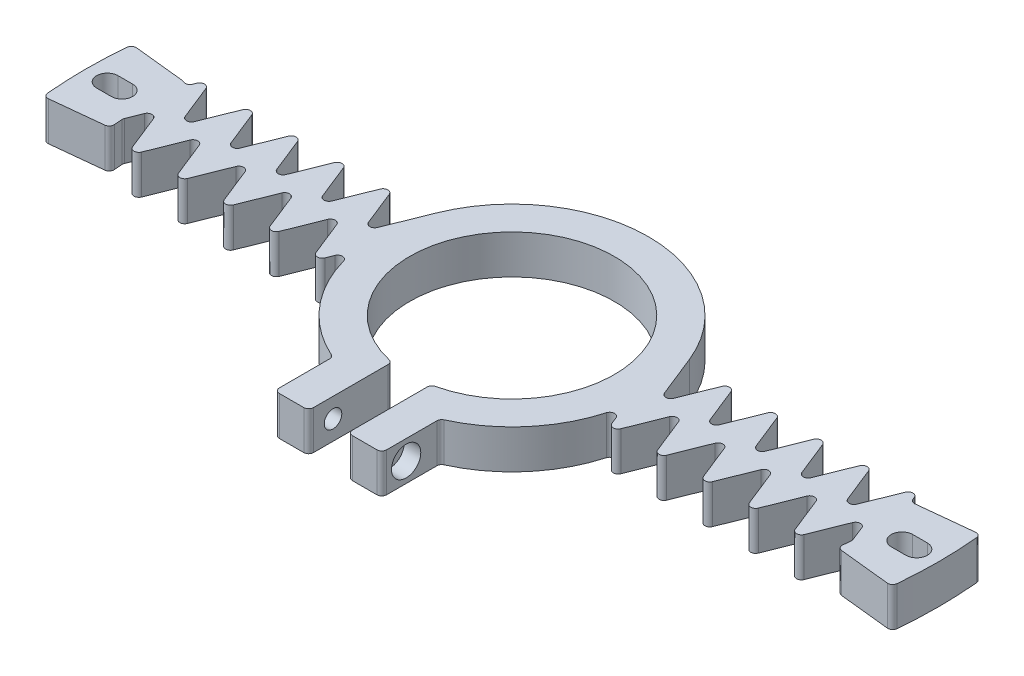
SolidWorks part; units mm, degrees
ref_plane "前视基准面" through (0, 0, 0) normal (0, 0, 1) x (1, 0, 0)
ref_plane "上视基准面" through (0, 0, 0) normal (0, 1, 0) x (1, 0, 0)
ref_plane "右视基准面" through (0, 0, 0) normal (1, 0, 0) x (0, 0, -1)
other "Configuration Table"
sketch "草图1" plane through (0, 0, 0) normal (0, 1, 0) x (1, 0, 0)
  line L0 (-1012, 0) -> (0, 0) construction
  line L1 (28, 0) -> (30.35, -5.8794) construction
  line L2 (30.35, -5.8794) -> (35.05, 5.8794) construction
  line L3 (35.05, 5.8794) -> (39.75, -5.8794) construction
  line L4 (39.75, -5.8794) -> (44.45, 5.8794) construction
  line L5 (44.45, 5.8794) -> (49.15, -5.8794) construction
  line L6 (49.15, -5.8794) -> (53.85, 5.8794) construction
  line L7 (53.85, 5.8794) -> (58.55, -5.8794) construction
  line L8 (58.55, -5.8794) -> (63.25, 5.8794) construction
  line L9 (63.25, 5.8794) -> (67.95, -5.8794) construction
  line L10 (67.95, -5.8794) -> (72.65, 5.8794) construction
  line L11 (72.65, 5.8794) -> (75, 0) construction
  line L12 (28, 0) -> (75, 0) construction
  line L15 (-4, -20.6155) -> (-4, -37.7128)
  line L16 (0, 0) -> (0, -50000) construction
  line L17 (11, -37.7128) -> (11, -25.7488)
  line L20 (87.0207, -9.1462) -> (74.5891, -7.8396)
  line L21 (87.0207, 9.1462) -> (74.5891, 7.8396)
  line L22 (-28, 0) -> (-75, 0) construction
  line L23 (-72.65, 5.8794) -> (-75, 0) construction
  line L24 (-67.95, -5.8794) -> (-72.65, 5.8794) construction
  line L29 (-63.25, 5.8794) -> (-67.95, -5.8794) construction
  line L30 (-58.55, -5.8794) -> (-63.25, 5.8794) construction
  line L31 (27.6386, -4.4844) -> (30.35, -11.268)
  line L32 (30.35, -11.268) -> (35.05, 0.4907)
  line L33 (35.05, 0.4907) -> (39.75, -11.268)
  line L34 (39.75, -11.268) -> (44.45, 0.4907)
  line L35 (44.45, 0.4907) -> (49.15, -11.268)
  line L36 (49.15, -11.268) -> (53.85, 0.4907)
  line L37 (53.85, 0.4907) -> (58.55, -11.268)
  line L38 (58.55, -11.268) -> (63.25, 0.4907)
  line L39 (63.25, 0.4907) -> (67.95, -11.268)
  line L40 (67.95, -11.268) -> (72.65, 0.4907)
  line L41 (72.65, 0.4907) -> (74.8348, -4.9753)
  line L42 (26, 10.3923) -> (30.35, -0.4907)
  line L43 (30.35, -0.4907) -> (35.05, 11.268)
  line L44 (35.05, 11.268) -> (39.75, -0.4907)
  line L45 (39.75, -0.4907) -> (44.45, 11.268)
  line L46 (44.45, 11.268) -> (49.15, -0.4907)
  line L47 (49.15, -0.4907) -> (53.85, 11.268)
  line L48 (53.85, 11.268) -> (58.55, -0.4907)
  line L49 (58.55, -0.4907) -> (63.25, 11.268)
  line L50 (63.25, 11.268) -> (67.95, -0.4907)
  line L51 (67.95, -0.4907) -> (72.65, 11.268)
  line L52 (72.65, 11.268) -> (74.7606, 5.9875)
  line L53 (29.8571, 0.7423) -> (30.35, -0.4907) construction
  line L54 (72.65, 0.4907) -> (73.1429, -0.7423) construction
  line L55 (-53.85, 5.8794) -> (-58.55, -5.8794) construction
  line L56 (-49.15, -5.8794) -> (-53.85, 5.8794) construction
  line L57 (-44.45, 5.8794) -> (-49.15, -5.8794) construction
  line L58 (-39.75, -5.8794) -> (-44.45, 5.8794) construction
  line L59 (-35.05, 5.8794) -> (-39.75, -5.8794) construction
  line L60 (-30.35, -5.8794) -> (-35.05, 5.8794) construction
  line L61 (-28, 0) -> (-30.35, -5.8794) construction
  line L62 (1012, 0) -> (0, 0) construction
  line L63 (-72.65, 11.268) -> (-74.7606, 5.9875)
  line L64 (-67.95, -0.4907) -> (-72.65, 11.268)
  line L65 (-63.25, 11.268) -> (-67.95, -0.4907)
  line L67 (-50000, 0) -> (50000, 0) construction
  line L70 (-58.55, -0.4907) -> (-63.25, 11.268)
  line L71 (-53.85, 11.268) -> (-58.55, -0.4907)
  line L72 (26.1429, -0.7423) -> (30.35, -11.268) construction
  line L73 (-49.15, -0.4907) -> (-53.85, 11.268)
  line L74 (72.65, 11.268) -> (76.8571, 0.7423) construction
  line L75 (-44.45, 11.268) -> (-49.15, -0.4907)
  line L76 (-39.75, -0.4907) -> (-44.45, 11.268)
  line L77 (-35.05, 11.268) -> (-39.75, -0.4907)
  line L78 (-30.35, -0.4907) -> (-35.05, 11.268)
  line L79 (-26, 10.3923) -> (-30.35, -0.4907)
  line L80 (-72.65, 0.4907) -> (-74.8348, -4.9753)
  line L81 (-67.95, -11.268) -> (-72.65, 0.4907)
  line L82 (-63.25, 0.4907) -> (-67.95, -11.268)
  line L83 (-58.55, -11.268) -> (-63.25, 0.4907)
  line L84 (-53.85, 0.4907) -> (-58.55, -11.268)
  line L85 (-49.15, -11.268) -> (-53.85, 0.4907)
  line L86 (-44.45, 0.4907) -> (-49.15, -11.268)
  line L87 (-39.75, -11.268) -> (-44.45, 0.4907)
  line L88 (-35.05, 0.4907) -> (-39.75, -11.268)
  line L89 (-30.35, -11.268) -> (-35.05, 0.4907)
  line L90 (-27.6386, -4.4844) -> (-30.35, -11.268)
  line L91 (-87.0207, 9.1462) -> (-74.5891, 7.8396)
  line L92 (-87.0207, -9.1462) -> (-74.5891, -7.8396)
  line L93 (-4, -37.7128) -> (-11, -37.7128)
  line L94 (-11, -37.7128) -> (-11, -25.7488)
  line L95 (4, -37.7128) -> (11, -37.7128)
  line L96 (4, -20.6155) -> (4, -37.7128)
  arc A2 (0, 87.5) -> (-87.5, 0) centre (0, 0) ccw construction
  arc A4 (0, 75) -> (-74.7606, 5.9875) centre (0, 0) ccw construction
  arc A10 (0, -28) -> (4, -27.7128) centre (0, 0) ccw construction
  arc A12 (-11, -25.7488) -> (-4, -27.7128) centre (0, 0) ccw construction
  arc A13 (-11, -25.7488) -> (-4, -27.7128) centre (0, 0) ccw construction
  arc A14 (4, -20.6155) -> (-4, -20.6155) centre (0, 0) ccw
  arc A15 (28, 0) -> (26, 10.3923) centre (0, 0) ccw construction
  arc A16 (26, 10.3923) -> (-26, 10.3923) centre (0, 0) ccw
  arc A17 (27.6386, -4.4844) -> (28, 0) centre (0, 0) ccw construction
  arc A18 (74.5891, 7.8396) -> (-74.5891, 7.8396) centre (0, 0) ccw construction
  arc A19 (87.0207, 9.1462) -> (-87.0207, 9.1462) centre (0, 0) ccw construction
  arc A20 (-87.0207, -9.1462) -> (87.0207, -9.1462) centre (0, 0) ccw construction
  arc A21 (87.0207, -9.1462) -> (87.0207, 9.1462) centre (0, 0) ccw
  arc A22 (-74.5891, -7.8396) -> (74.5891, -7.8396) centre (0, 0) ccw construction
  arc A23 (74.5891, -7.8396) -> (74.8348, -4.9753) centre (0, 0) ccw
  arc A24 (-74.8348, -4.9753) -> (0, -75) centre (0, 0) ccw construction
  arc A25 (-87.5, 0) -> (0, -87.5) centre (0, 0) ccw construction
  arc A26 (74.8348, -4.9753) -> (75, 0) centre (0, 0) ccw construction
  arc A27 (74.7606, 5.9875) -> (74.5891, 7.8396) centre (0, 0) ccw
  arc A28 (75, 0) -> (74.7606, 5.9875) centre (0, 0) ccw construction
  arc A29 (-75, 0) -> (-74.7606, 5.9875) centre (0, 0) cw construction
  arc A30 (-74.8348, -4.9753) -> (-75, 0) centre (0, 0) cw construction
  arc A31 (-74.7606, 5.9875) -> (-74.5891, 7.8396) centre (0, 0) cw
  arc A32 (-74.5891, -7.8396) -> (-74.8348, -4.9753) centre (0, 0) cw
  arc A33 (-87.0207, -9.1462) -> (-87.0207, 9.1462) centre (0, 0) cw
  arc A34 (-28, 0) -> (-27.6386, -4.4844) centre (0, 0) ccw construction
  arc A35 (-27.6386, -4.4844) -> (-11, -25.7488) centre (0, 0) ccw
  arc A36 (-26, 10.3923) -> (-28, 0) centre (0, 0) ccw construction
  arc A37 (0, -28) -> (4, -27.7128) centre (0, 0) ccw construction
  arc A38 (-4, -27.7128) -> (0, -28) centre (0, 0) ccw construction
  arc A39 (-4, -27.7128) -> (0, -28) centre (0, 0) ccw construction
  arc A40 (-4, -20.6155) -> (0, -21) centre (0, 0) ccw construction
  arc A41 (4, -27.7128) -> (11, -25.7488) centre (0, 0) ccw construction
  arc A42 (11, -25.7488) -> (27.6386, -4.4844) centre (0, 0) ccw
  arc A43 (4, -27.7128) -> (11, -25.7488) centre (0, 0) ccw construction
  arc A44 (11, -25.7488) -> (27.6386, -4.4844) centre (0, 0) ccw
  arc A45 (-26, 10.3923) -> (-28, 0) centre (0, 0) ccw construction
  arc A46 (-27.6386, -4.4844) -> (-11, -25.7488) centre (0, 0) ccw
  arc A47 (-28, 0) -> (-27.6386, -4.4844) centre (0, 0) ccw construction
  arc A48 (28, 0) -> (26, 10.3923) centre (0, 0) ccw construction
  arc A49 (26, 10.3923) -> (-26, 10.3923) centre (0, 0) ccw
  arc A50 (27.6386, -4.4844) -> (28, 0) centre (0, 0) ccw construction
  arc A51 (-74.7606, 5.9875) -> (-75, 0) centre (0, 0) ccw construction
  arc A52 (-75, 0) -> (-74.8348, -4.9753) centre (0, 0) ccw construction
  arc A53 (0, -21) -> (4, -20.6155) centre (0, 0) ccw construction
  point P10 (32.7, 0)
  point P112 (-4, -27.7128)
  dimension "D1" = 150
  dimension "D2" = 56
  dimension "D3" = 175
  dimension "D4" = 42
  dimension "D5" = 4
  dimension "D7" = 6
  dimension "D10" = 6
  dimension "D11" = 10
  dimension "D12" = 7
  dimension "D8" = 2
  dimension "D9" = 2
extrude "凸台-拉伸1" add sketch "草图1" along normal blind 8
sketch "草图2" plane through (0, 8, 0) normal (0, 1, 0) x (1, 0, 0)
  line L0 (-83, 0) -> (-80, 0) construction
  line L1 (0, 0) -> (0, 50000) construction
  line L2 (-83, -2.2) -> (-80, -2.2)
  line L7 (-83, 2.2) -> (-80, 2.2)
  line L8 (83, 2.2) -> (80, 2.2)
  line L9 (83, -2.2) -> (80, -2.2)
  circle A5 centre (0, 0) radius 81.5 construction
  arc A6 (-83, -2.2) -> (-83, 2.2) centre (-83, 0) cw
  arc A7 (-80, -2.2) -> (-80, 2.2) centre (-80, 0) ccw
  arc A8 (83, -2.2) -> (83, 2.2) centre (83, 0) ccw
  arc A9 (80, -2.2) -> (80, 2.2) centre (80, 0) cw
  point P3 (0, 0)
  point P6 (-81.5, 0)
  dimension "D1" = 163
  dimension "D2" = 3
  dimension "D3" = 2.2
  dimension "D4" = 2.2
extrude "切除-拉伸1" cut sketch "草图2" against normal through all
hole_wizard "M3 六角圆柱头螺钉的柱形沉头孔1" positions "草图5" profile "草图6" counterbore size "M3" standard "GB" end condition through all
sketch "草图5" plane through (11, 0, 0) normal (1, 0, 0) x (0, 0, -1)
  line L2 (-37.7128, 8) -> (-25.7488, 8) construction
  line L3 (-32.7128, 4) -> (-32.7128, 8) construction
  line L5 (-32.7128, 4) -> (-32.7128, 0) construction
  line L6 (-37.7128, 0) -> (-25.7488, 0) construction
  line L8 (-37.7128, 8) -> (-37.7128, 0) construction
  line L9 (-25.7488, 8) -> (-25.7488, 0) construction
  point P0 (-32.7128, 4)
  dimension "D1" = 5
  dimension "D2" = 6.964
sketch "草图6" plane through (11, 4, 32.7128) normal (0, 1, 0) x (0, 0, -1)
  line L0 (0, 0) -> (0, 98.5)
  line L1 (0, 98.5) -> (1.8, 98.5)
  line L3 (1.8, 98.5) -> (1.8, 3.4)
  line L4 (1.8, 3.4) -> (3, 3.4)
  line L5 (3, 3.4) -> (3, 0)
  line L7 (3, 0) -> (0, 0)
  line L11 (0, -6.35) -> (0, 107.95) construction
  dimension "通孔孔直径" = 3.6
  dimension "通孔孔深度" = 98.5
  dimension "柱形沉头孔直径" = 6
  dimension "柱形沉头孔深度" = 3.4
sketch "草图7" plane through (-11, 0, 0) normal (-1, 0, 0) x (0, 0, 1)
  line L1 (34.4449, 1) -> (36.1769, 4)
  line L2 (36.1769, 4) -> (34.4449, 7)
  line L3 (34.4449, 7) -> (30.9808, 7)
  line L4 (30.9808, 7) -> (29.2487, 4)
  line L5 (29.2487, 4) -> (30.9808, 1)
  line L6 (30.9808, 1) -> (34.4449, 1)
  circle A2 centre (32.7128, 4) radius 3 construction
  dimension "D1" = 6
extrude "切除-拉伸2" cut sketch "草图7" against normal blind 3
fillet "圆角1" radius 1 14 edges at (30.35, 4, 11.268) (-87.0207, 4, 9.1462) (-74.5891, 4, -7.8396) (-63.25, 4, -11.268) (-67.95, 4, 0.4907) (-72.65, 4, -11.268) (30.35, 4, 0.4907) (-30.35, 4, 0.4907) (-35.05, 4, -11.268) (-39.75, 4, 0.4907) (-44.45, 4, -11.268) (-49.15, 4, 0.4907) (-53.85, 4, -11.268) (-58.55, 4, 0.4907)
fillet "圆角2" radius 1 19 edges at (-74.7606, 4, -5.9875) (-44.45, 4, -0.4907) (-49.15, 4, 11.268) (-53.85, 4, -0.4907) (-58.55, 4, 11.268) (-63.25, 4, -0.4907) (-67.95, 4, 11.268) (-72.65, 4, -0.4907) (-74.8348, 4, 4.9753) (35.05, 4, -11.268) (39.75, 4, 0.4907) (44.45, 4, -11.268) (49.15, 4, 0.4907) (53.85, 4, -11.268) (58.55, 4, 0.4907) (63.25, 4, -11.268) (67.95, 4, 0.4907) (-87.0207, 4, -9.1462) (-74.5891, 4, 7.8396)
fillet "圆角3" radius 1 7 edges at (74.7606, 4, -5.9875) (74.8348, 4, 4.9753) (87.0207, 4, 9.1462) (87.0207, 4, -9.1462) (74.5891, 4, 7.8396) (72.65, 4, -0.4907) (72.65, 4, -11.268)
fillet "圆角4" radius 1 22 edges at (74.5891, 4, -7.8396) (27.6386, 4, 4.4844) (11, 4, 25.7488) (4, 4, 20.6155) (4, 4, 37.7128) (11, 4, 37.7128) (-4, 4, 20.6155) (67.95, 4, 11.268) (63.25, 4, -0.4907) (58.55, 4, 11.268) (53.85, 4, -0.4907) (49.15, 4, 11.268) (44.45, 4, -0.4907) (39.75, 4, 11.268) (35.05, 4, -0.4907) (-11, 4, 25.7488) (-11, 4, 37.7128) (-4, 4, 37.7128) (-27.6386, 4, 4.4844) (-30.35, 4, 11.268) (-35.05, 4, -0.4907) (-39.75, 4, 11.268)
